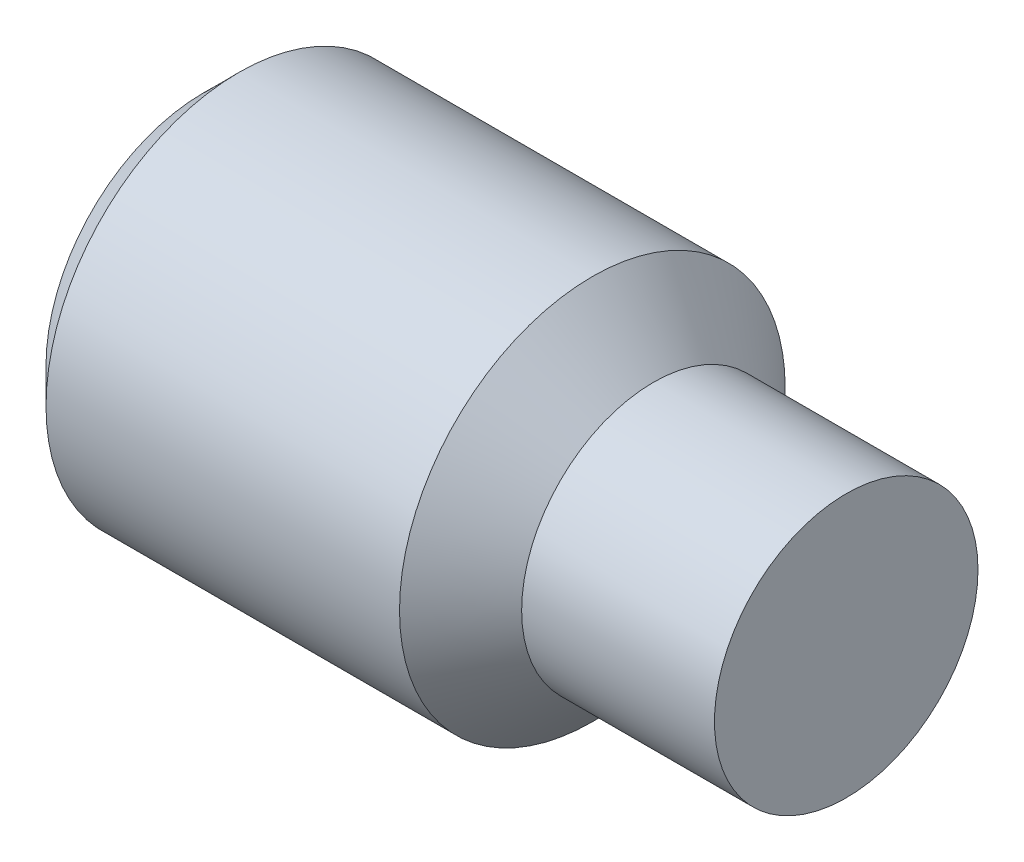
SolidWorks part; units mm, degrees
note: '?' marks a value the reader was unsure of.
ref_plane "Спереди" through (0, 0, 0) normal (0, 0, 1) x (1, 0, 0)
ref_plane "Сверху" through (0, 0, 0) normal (0, 1, 0) x (1, 0, 0)
ref_plane "Справа" through (0, 0, 0) normal (1, 0, 0) x (0, 0, -1)
sketch "Эскиз1" plane through (0, 0, 0) normal (1, 0, 0) x (0, 0, -1)
  circle A0 centre (0, 0) radius 6
  dimension "D1" = 12
extrude "Вытянуть1" add sketch "Эскиз1" along normal blind 20
sketch "Эскиз2" plane through (0, 0, 0) normal (-1, 0, 0) x (0, 0, 1)
  line L0 (0, 3.4641) -> (-3, 1.7321)
  line L1 (-3, 1.7321) -> (-3, -1.7321)
  line L2 (-3, -1.7321) -> (0, -3.4641)
  line L3 (0, -3.4641) -> (3, -1.7321)
  line L4 (3, -1.7321) -> (3, 1.7321)
  line L5 (3, 1.7321) -> (0, 3.4641)
  line L6 (0, -3.4641) -> (0, 3.4641) construction
  circle A0 centre (0, 0) radius 3.4641
  dimension "D1" = 120
  dimension "D2" = 120
  dimension "D3" = 6
extrude "Вырез-Вытянуть1" cut sketch "Эскиз2" against normal blind 8 contours L2 L6 L0 L1 | L6 L3 L4 L5
sketch "Эскиз3" plane through (20, 0, 0) normal (1, 0, 0) x (0, 0, -1)
  circle A0 centre (0, 0) radius 6
  circle A1 centre (0, 0) radius 4.1
  circle A2 centre (0, 0) radius 6 construction
  dimension "D1" = 8.2
extrude "Вырез-Вытянуть2" cut sketch "Эскиз3" against normal blind 6
sketch "Эскиз4" plane through (0, 0, 0) normal (0, 0, 1) x (1, 0, 0)
  line L0 (0, 0) -> (20, 0) construction
  line L1 (20, -4.1) -> (20, 4.1) construction
  line L2 (14, 6) -> (14, 4.1)
  line L3 (14, 4.1) -> (12.1, 6)
  line L4 (12.1, 6) -> (14, 6)
  line L5 (14, 6) -> (13.8844, 5.9345)
  dimension "D1" = 45
revolve "Вырез-Повернуть1" cut sketch "Эскиз4" angle 360 about L0
sketch "Эскиз5" plane through (0, 0, 0) normal (0, 0, 1) x (1, 0, 0)
  line L0 (0, 0) -> (12.1, 0) construction
  line L1 (12.1, 6) -> (12.1, -6) construction
  line L2 (0, 6) -> (0, 4.9)
  line L3 (0, 6) -> (0, -6) construction
  line L4 (0, 4.9) -> (1.1, 6)
  line L5 (1.1, 6) -> (0, 6)
  dimension "D1" = 45
  dimension "D2" = 4.9
revolve "Вырез-Повернуть2" cut sketch "Эскиз5" angle 360 about L0
ref_axis "Ось1" through (21.5951, 0, 0) along (-1, 0, 0)?
fillet "Скругление1" radius 1 6 edges at (8, 0, -3) (8, 2.5981, -1.5) (8, 2.5981, 1.5) (8, 0, 3) (8, -2.5981, 1.5) (8, -2.5981, -1.5)
